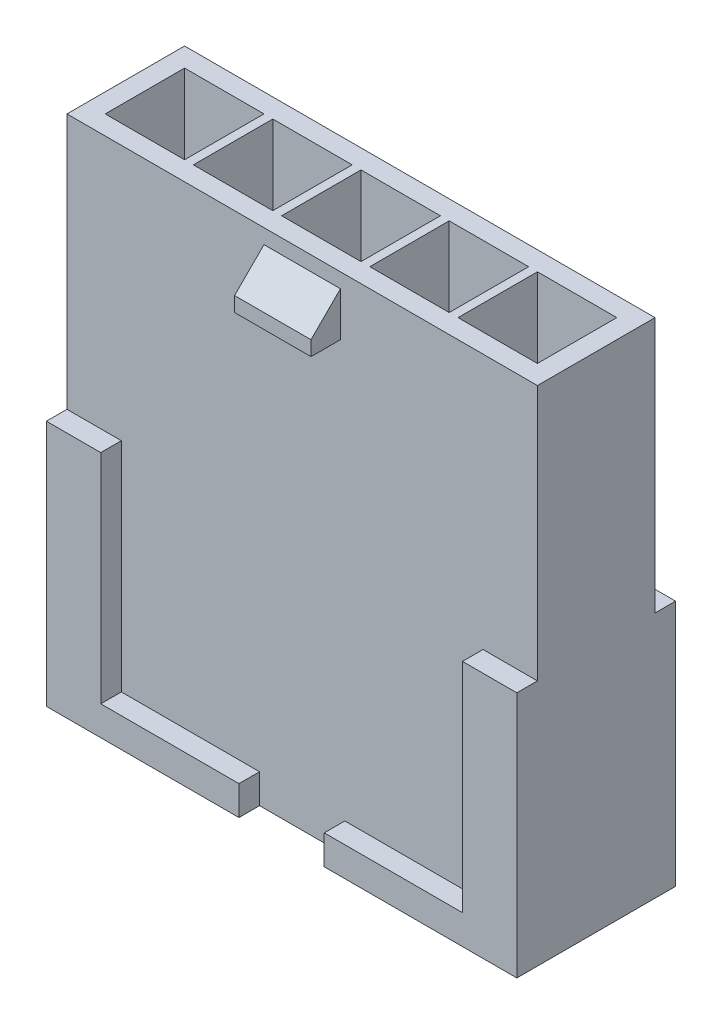
SolidWorks part; units mm, degrees
ref_plane "Front Plane" through (0, 0, 0) normal (0, 0, 1) x (1, 0, 0)
ref_plane "Top Plane" through (0, 0, 0) normal (0, 1, 0) x (1, 0, 0)
ref_plane "Right Plane" through (0, 0, 0) normal (1, 0, 0) x (0, 0, -1)
sketch "Sketch1" plane through (0, 0, 0) normal (0, 1, 0) x (1, 0, 0)
  line L0 (1.65, 1.35) -> (4.35, 1.35)
  line L1 (-8, 2) -> (8, 2)
  line L2 (-8, 2) -> (-8, -2)
  line L3 (-8, -2) -> (8, -2)
  line L4 (8, 2) -> (8, -2)
  line L5 (-8, 2) -> (8, -2) construction
  line L6 (-8, -2) -> (8, 2) construction
  line L7 (-1.35, 1.35) -> (1.35, 1.35)
  line L8 (-1.35, 1.35) -> (-1.35, -1.35)
  line L9 (-1.35, -1.35) -> (1.35, -1.35)
  line L10 (1.35, 1.35) -> (1.35, -1.35)
  line L11 (-1.35, 1.35) -> (1.35, -1.35) construction
  line L12 (-1.35, -1.35) -> (1.35, 1.35) construction
  line L13 (4.35, 1.35) -> (4.35, -1.35)
  line L14 (1.65, -1.35) -> (4.35, -1.35)
  line L15 (1.65, 1.35) -> (1.65, -1.35)
  line L16 (4.65, 1.35) -> (7.35, 1.35)
  line L17 (7.35, 1.35) -> (7.35, -1.35)
  line L18 (4.65, -1.35) -> (7.35, -1.35)
  line L19 (4.65, 1.35) -> (4.65, -1.35)
  line L20 (0, 2) -> (0, -2) construction
  line L21 (-4.65, 1.35) -> (-4.65, -1.35)
  line L22 (-4.65, 1.35) -> (-7.35, 1.35)
  line L23 (-7.35, 1.35) -> (-7.35, -1.35)
  line L24 (-4.65, -1.35) -> (-7.35, -1.35)
  line L25 (-1.65, 1.35) -> (-1.65, -1.35)
  line L26 (-1.65, 1.35) -> (-4.35, 1.35)
  line L27 (-4.35, 1.35) -> (-4.35, -1.35)
  line L28 (-1.65, -1.35) -> (-4.35, -1.35)
  point P0 (0, 0)
  point P6 (0, 0)
  dimension "D1" = 4
  dimension "D2" = 16
  dimension "D3" = 2.7
  dimension "D5" = 3
  dimension "D4" = 3
extrude "Boss-Extrude1" add sketch "Sketch1" along normal blind 17.1
sketch "Sketch2" plane through (0, 0, 2) normal (0, 0, 1) x (1, 0, 0)
  line L0 (0, 17.1) -> (0, 0) construction
  line L1 (-8, 17.1) -> (8, 17.1) construction
  line L2 (-8, 17.1) -> (-8, 0) construction
  line L3 (-8, 8.4) -> (-6.15, 8.4)
  line L4 (-8, 8.4) -> (-8, 0)
  line L5 (-8, 0) -> (-6.15, 0)
  line L6 (-6.15, 8.4) -> (-6.15, 0)
  line L7 (-8, 0) -> (8, 0) construction
  line L8 (1.45, 1) -> (1.45, 0)
  line L9 (-6.15, 1) -> (-1.45, 1)
  line L10 (-6.15, 1) -> (-6.15, 0)
  line L11 (-6.15, 0) -> (-1.45, 0)
  line L12 (-1.45, 1) -> (-1.45, 0)
  line L13 (6.15, 1) -> (1.45, 1)
  line L14 (8, 0) -> (6.15, 0)
  line L15 (8, 8.4) -> (8, 0)
  line L16 (8, 8.4) -> (6.15, 8.4)
  line L17 (6.15, 8.4) -> (6.15, 0)
  line M10 (-8, 0) -> (8, 0)
  line M11 (8, 0) -> (8, 17.1)
  line M13 (-8, 17.1) -> (-8, 0)
  dimension "D1" = 8.4
  dimension "D2" = 1.85
  dimension "D3" = 1
  dimension "D4" = 2.9
extrude "Boss-Extrude2" add sketch "Sketch2" along normal blind 0.7 contours L6 L3 M13 M10 | L12 L9 L6 M10 | L17 L13 L8 M10 | L16 L17 M10 M11 region at (3.8, 0.5, 2) region at (-7.075, 4.2, 2) region at (-3.8, 0.5, 2) region at (7.075, 4.2, 2)
sketch "Sketch3" plane through (0, 0, 0) normal (1, 0, 0) x (0, 0, -1)
  line L0 (-2, 16.6) -> (-3, 15.6)
  line L1 (-2, 17.1) -> (-2, 8.4) construction
  line L2 (-3, 15.6) -> (-3, 15.1)
  line L3 (-3, 15.1) -> (-2, 15.1)
  line L4 (-2, 15.1) -> (-2, 16.6)
  line L5 (-2, 17.1) -> (2, 17.1) construction
  dimension "D1" = 0.5
  dimension "D2" = 1
  dimension "D3" = 0.5
  dimension "D4" = 45
extrude "Boss-Extrude3" add sketch "Sketch3" along normal mid plane 2.6
sketch "Sketch4" plane through (0, 0, -2) normal (0, 0, -1) x (-1, 0, 0)
  line L0 (6.15, 1) -> (6.15, 8.4) construction
  line L1 (6.15, 8.4) -> (8, 8.4) construction
  line L2 (8, 8.4) -> (8, 0) construction
  line L3 (8, 0) -> (1.45, 0) construction
  line L4 (1.45, 0) -> (1.45, 1) construction
  line L5 (1.45, 1) -> (6.15, 1) construction
  line L6 (-1.45, 0) -> (-8, 0) construction
  line L7 (-8, 0) -> (-8, 8.4) construction
  line L8 (-8, 8.4) -> (-6.15, 8.4) construction
  line L9 (-6.15, 8.4) -> (-6.15, 1) construction
  line L10 (-6.15, 1) -> (-1.45, 1) construction
  line L11 (-1.45, 1) -> (-1.45, 0) construction
  line L12 (6.15, 1) -> (6.15, 8.4)
  line L13 (6.15, 8.4) -> (8, 8.4)
  line L14 (8, 8.4) -> (8, 0)
  line L15 (8, 0) -> (1.45, 0)
  line L16 (1.45, 0) -> (1.45, 1)
  line L17 (1.45, 1) -> (6.15, 1)
  line L18 (-1.45, 0) -> (-8, 0)
  line L19 (-8, 0) -> (-8, 8.4)
  line L20 (-8, 8.4) -> (-6.15, 8.4)
  line L21 (-6.15, 8.4) -> (-6.15, 1)
  line L22 (-6.15, 1) -> (-1.45, 1)
  line L23 (-1.45, 1) -> (-1.45, 0)
  line L25 (-1.45, 1) -> (1.45, 1)
  line L26 (-1.45, 1) -> (-1.45, 0)
  line L27 (-1.45, 0) -> (1.45, 0)
  line L28 (1.45, 1) -> (1.45, 0)
  line M1 (-8, 0) -> (8, 0)
  line M2 (8, 0) -> (8, 17.1)
  line M4 (-8, 17.1) -> (-8, 0)
extrude "Boss-Extrude4" add sketch "Sketch4" along normal blind 0.7 contours L23 L22 L21 L20 M4 M1 | L25 L23 L16 M1 | L17 L16 L13 L12 M1 M2 region at (-6.3145, 3.3408, -2) region at (0, 0.5, -2) region at (6.3145, 3.3408, -2)
